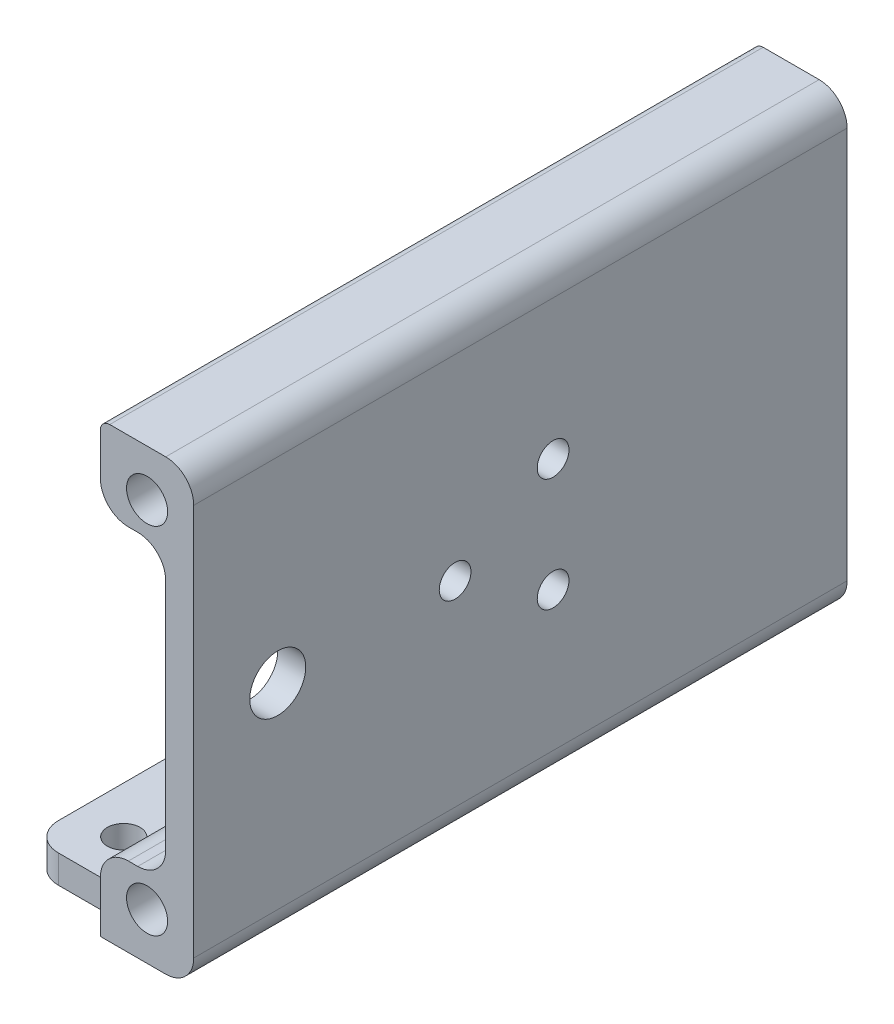
SolidWorks part; units mm, degrees
ref_plane "Front Plane" through (0, 0, 0) normal (0, 0, 1) x (1, 0, 0)
ref_plane "Top Plane" through (0, 0, 0) normal (0, 1, 0) x (1, 0, 0)
ref_plane "Right Plane" through (0, 0, 0) normal (1, 0, 0) x (0, 0, -1)
sketch "Sketch1" plane through (0, 0, 0) normal (0, 0, 1) x (1, 0, 0)
  line L0 (54, -19) -> (54, 19) construction
  line L1 (49, 24) -> (49, 18.5)
  line L2 (49, 24) -> (56, 24)
  line L4 (49, -24) -> (56, -24)
  line L5 (59, 21) -> (59, -21)
  line L6 (49, 24) -> (59, -24) construction
  line L7 (49, -24) -> (59, 24) construction
  line L8 (52, 15.5) -> (53, 15.5)
  line L9 (56, 12.5) -> (56, -12.5)
  line L10 (53, -15.5) -> (52, -15.5)
  line L11 (49, -18.5) -> (49, -24)
  arc A0 (56, -24) -> (59, -21) centre (56, -21) ccw
  arc A1 (59, 21) -> (56, 24) centre (56, 21) ccw
  arc A2 (56, -12.5) -> (53, -15.5) centre (53, -12.5) cw
  arc A3 (56, 12.5) -> (53, 15.5) centre (53, 12.5) ccw
  arc A4 (52, -15.5) -> (49, -18.5) centre (52, -18.5) ccw
  arc A5 (52, 15.5) -> (49, 18.5) centre (52, 18.5) cw
  point P4 (54, 0)
  dimension "D3" = 3
  dimension "D4" = 3
  dimension "D5" = 3
  dimension "D6" = 3
  dimension "D1" = 10
  dimension "D2" = 48
  dimension "D7" = 7
  dimension "D8" = 5.5
extrude "Boss-Extrude1" add sketch "Sketch1" along normal blind 70
sketch "Sketch2" plane through (0, 0, 0) normal (0, 0, -1) x (-1, 0, 0)
  circle A0 centre (-54, -19) radius 2.2
  circle A1 centre (-54, 19) radius 2.2
  dimension "D1" = 4.4
ref_plane "Plane1" through (0, 0, 35) normal (0, 0, -1) x (-1, 0, 0)
extrude "Cut-Extrude1" cut sketch "Sketch2" against normal blind 5.3
mirror "Mirror1" about plane through (0, 0, 35) normal (0, 0, -1) of "Cut-Extrude1"
fillet "Fillet1" radius 1 1 edges at (49, 24, 35)
sketch "Sketch4" plane through (59, 0, 0) normal (1, 0, 0) x (0, 0, -1)
  line L0 (-42, 0) -> (-35, 0) construction
  line L1 (-35, 0) -> (-31.5, 6.0622) construction
  line L2 (-35, 0) -> (-31.5, -6.0622) construction
  line L4 (-70, 0) -> (-35, 0) construction
  line L5 (-70, -21) -> (-70, 21) construction
  circle A0 centre (-42, 0) radius 1.7
  circle A1 centre (-31.5, 6.0622) radius 1.7
  circle A2 centre (-31.5, -6.0622) radius 1.7
  circle A3 centre (-35, 0) radius 7 construction
  circle A4 centre (-61, 0) radius 3
  dimension "D1" = 14
  dimension "D2" = 3.4
  dimension "D6" = 9
  dimension "D7" = 6
  dimension "D3" = 120
  dimension "D4" = 120
  dimension "D5" = 35
extrude "Cut-Extrude3" cut sketch "Sketch4" against normal blind 10
sketch "Sketch5" plane through (0, -24, 0) normal (0, -1, 0) x (1, 0, 0)
  line L0 (49, 35) -> (39, 35) construction
  line L1 (49, 70) -> (49, 0) construction
  line L2 (44, 35) -> (44, 62.5) construction
  line L3 (49, 2.5) -> (42, 2.5)
  line L4 (49, 2.5) -> (49, 67.5)
  line L5 (49, 67.5) -> (42, 67.5)
  line L6 (39, 5.5) -> (39, 64.5)
  line L7 (49, 2.5) -> (39, 67.5) construction
  line L8 (49, 67.5) -> (39, 2.5) construction
  arc A0 (39, 5.5) -> (42, 2.5) centre (42, 5.5) ccw
  arc A1 (39, 64.5) -> (42, 67.5) centre (42, 64.5) cw
  circle A2 centre (44, 62.5) radius 1.75
  circle A3 centre (44, 7.5) radius 1.75
  point P4 (44, 35)
  dimension "D3" = 3
  dimension "D5" = 3.5
  dimension "D1" = 65
  dimension "D2" = 10
  dimension "D4" = 5
extrude "Boss-Extrude2" add sketch "Sketch5" against normal blind 3
chamfer "Chamfer1" distance 1 angle 45 3 edges at (49, -22.5, 2.5) (49, -21, 35) (49, -22.5, 67.5)
